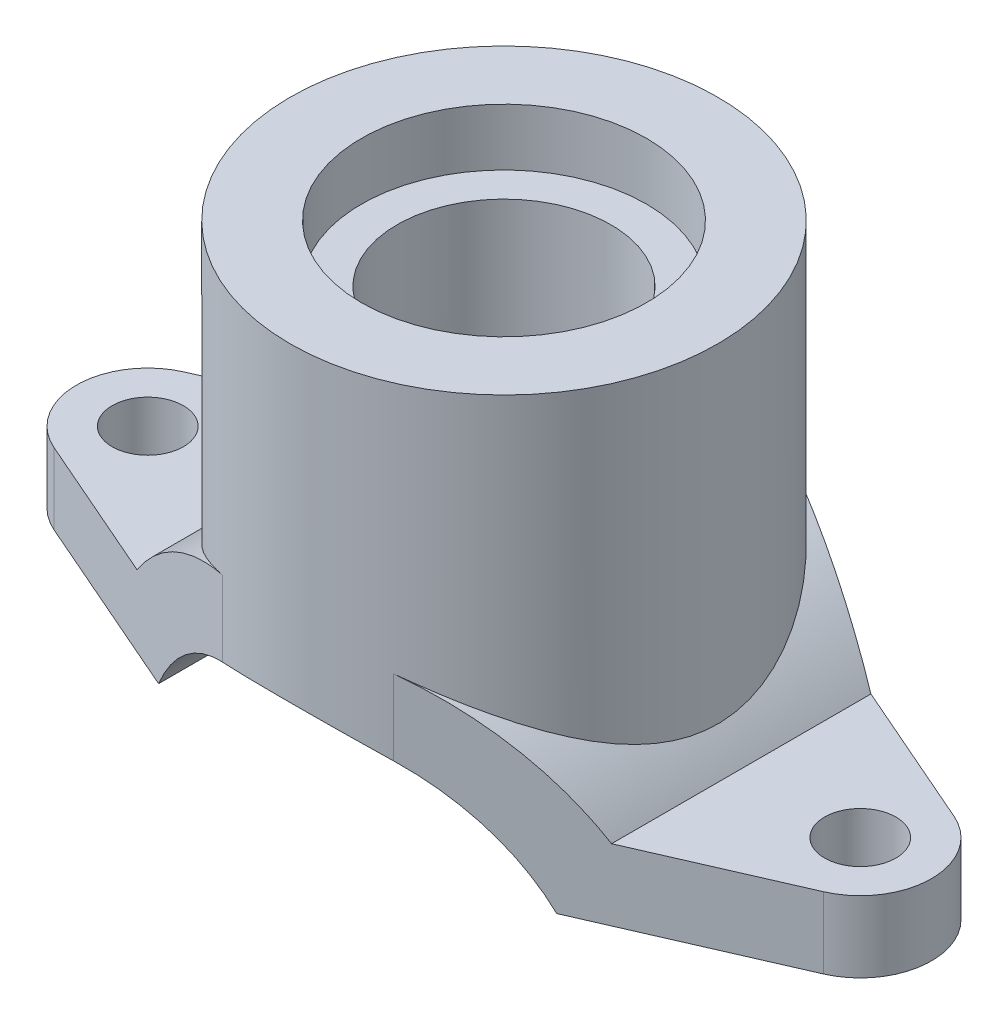
SolidWorks part; units mm, degrees
ref_plane "Front Plane" through (0, 0, 0) normal (0, 0, 1) x (1, 0, 0)
ref_plane "Top Plane" through (0, 0, 0) normal (0, 1, 0) x (1, 0, 0)
ref_plane "Right Plane" through (0, 0, 0) normal (1, 0, 0) x (0, 0, -1)
sketch "Sketch1" plane through (0, 0, 0) normal (0, 0, 1) x (1, 0, 0)
  line L0 (0, 0) -> (18248.7731, 0) construction
  line L1 (0, 0) -> (0, 18248.7731) construction
  line L3 (-150, 0) -> (150, 0)
  line L4 (-150, 0) -> (-150, 25)
  line L5 (-150, 25) -> (150, 25)
  line L6 (150, 0) -> (150, 25)
  arc A0 (69.8498, 0) -> (-69.8498, 0) centre (0, -39) ccw
  arc A1 (97.4885, 0) -> (-97.4885, 0) centre (0, -39) ccw
  point P14 (150, 12.5)
  dimension "D1" = 80
  dimension "D2" = 105
  dimension "D3" = 39
  dimension "D4" = 300
  dimension "D5" = 25
extrude "Boss-Extrude3" add sketch "Sketch1" along normal mid plane 150 contours A1 L5 L4 L3 | L5 A1 L3 A0 | L5 A1 A0 | L3 A1 L5 A0 | A1 L3 L6 L5 region at (-120.4194, 13.0016, 0) region at (-75.4363, 12.9984, 0) region at (0, 44.5951, 0) region at (75.4363, 12.9984, 0) region at (120.4194, 13.0016, 0)
sketch "Sketch2" plane through (0, 0, 0) normal (0, 1, 0) x (1, 0, 0)
  line L0 (0, 0) -> (50000, 0) construction
  line L1 (0, 0) -> (0, 50000) construction
  line L2 (-135, -22.9129) -> (-30, -68.7386)
  line L3 (-135, 22.9129) -> (-30, 68.7386)
  line L4 (135, -22.9129) -> (30, -68.7386)
  line L5 (135, 22.9129) -> (30, 68.7386)
  arc A0 (-30, -68.7386) -> (30, -68.7386) centre (0, 0) ccw
  circle A1 centre (125, 0) radius 12.5
  arc A2 (135, -22.9129) -> (135, 22.9129) centre (125, 0) ccw
  circle A3 centre (-125, 0) radius 12.5
  arc A4 (-135, -22.9129) -> (-135, 22.9129) centre (-125, 0) cw
  arc A5 (30, 68.7386) -> (-30, 68.7386) centre (0, 0) ccw
  dimension "D2" = 150
  dimension "D3" = 50
  dimension "D4" = 25
  dimension "D1" = 250
extrude "Cut-Extrude1" cut sketch "Sketch2" along normal blind 150 flip side to cut
ref_plane "Plane1" through (0, 150, 0) normal (0, 1, 0) x (1, 0, 0)
sketch "Sketch3" plane through (0, 150, 0) normal (0, 1, 0) x (1, 0, 0)
  circle A0 centre (0, 0) radius 75
  dimension "D1" = 150
extrude "Boss-Extrude4" add sketch "Sketch3" against normal up to next
sketch "Sketch4" plane through (0, 150, 0) normal (0, 1, 0) x (1, 0, 0)
  circle A0 centre (0, 0) radius 50
  circle A1 centre (0, 0) radius 37.5
  dimension "D1" = 75
  dimension "D2" = 100
extrude "Cut-Extrude2" cut sketch "Sketch4" against normal blind 150 contours A1 region at (0, 150, 0)
extrude "Cut-Extrude3" cut sketch "Sketch4<4>" against normal blind 20
sketch "Sketch4<4>" plane through (0, 150, 0) normal (0, 1, 0) x (1, 0, 0) same geometry as "Sketch4"
